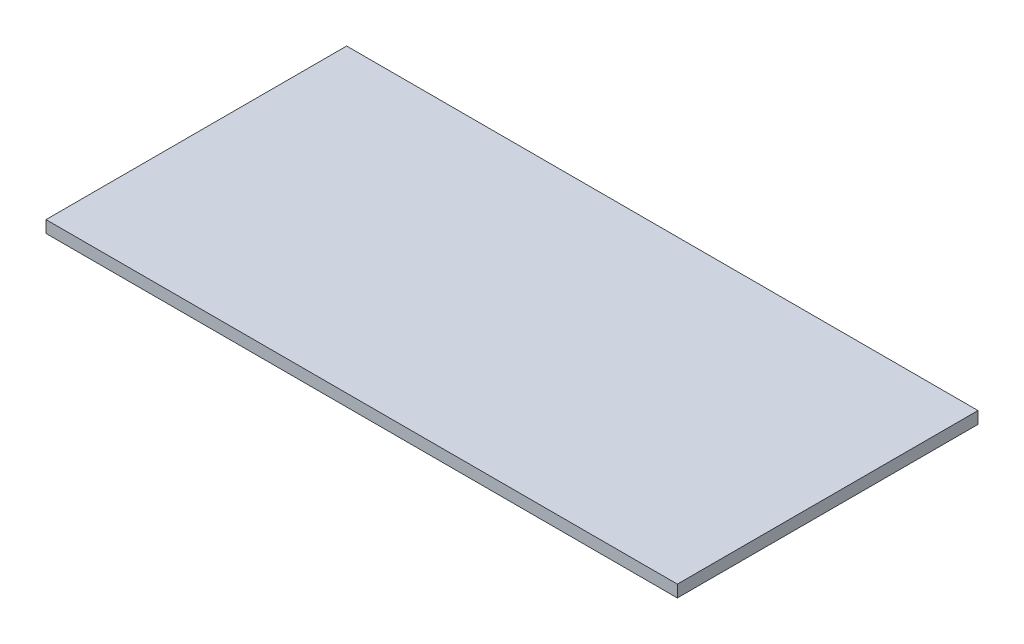
SolidWorks part; units mm, degrees
ref_plane "Front Plane" through (0, 0, 0) normal (0, 0, 1) x (1, 0, 0)
ref_plane "Top Plane" through (0, 0, 0) normal (0, 1, 0) x (1, 0, 0)
ref_plane "Right Plane" through (0, 0, 0) normal (1, 0, 0) x (0, 0, -1)
sketch "Sketch1" plane through (0, 0, 0) normal (0, 1, 0) x (1, 0, 0)
  line L1 (0, 0) -> (420, 0)
  line L2 (0, 0) -> (0, -200)
  line L3 (0, -200) -> (420, -200)
  line L4 (420, 0) -> (420, -200)
  dimension "D1" = 200
  dimension "D2" = 420
extrude "Boss-Extrude1" add sketch "Sketch1" along normal blind 8
